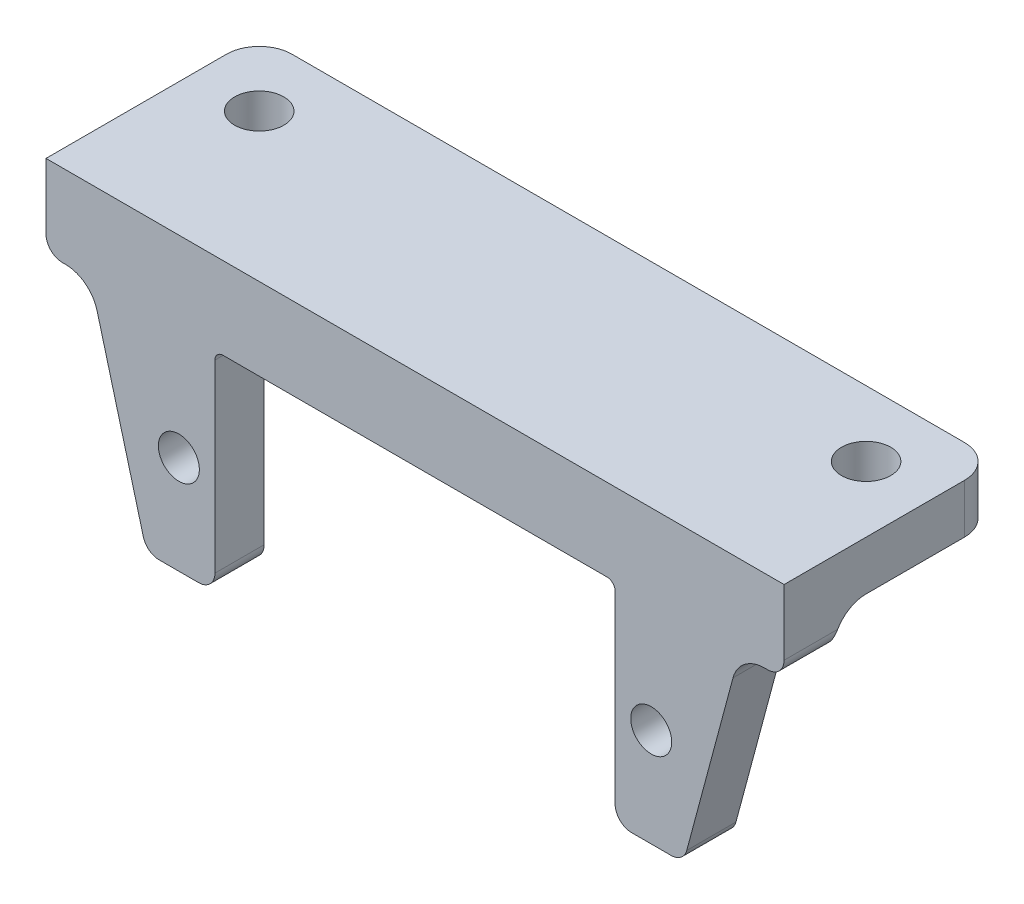
SolidWorks part; units mm, degrees
ref_plane "Front Plane" through (0, 0, 0) normal (0, 0, 1) x (1, 0, 0)
ref_plane "Top Plane" through (0, 0, 0) normal (0, 1, 0) x (1, 0, 0)
ref_plane "Right Plane" through (0, 0, 0) normal (1, 0, 0) x (0, 0, -1)
sketch "Sketch1" plane through (0, 0, 0) normal (0, 0, 1) x (1, 0, 0)
  line L1 (-15.9, -6.25) -> (15.9, -6.25)
  line L2 (-15.9, -6.25) -> (-15.9, 6.25)
  line L3 (-15.9, 6.25) -> (15.9, 6.25)
  line L4 (15.9, -6.25) -> (15.9, 6.25)
  line L5 (-15.9, -6.25) -> (15.9, 6.25) construction
  line L6 (-15.9, 6.25) -> (15.9, -6.25) construction
  line L7 (11.7, -6.25) -> (-11.7, -6.25)
  line L8 (11.7, -6.25) -> (11.7, 6.25)
  line L9 (11.7, 6.25) -> (-11.7, 6.25)
  line L10 (-11.7, -6.25) -> (-11.7, 6.25)
  line L11 (11.7, -6.25) -> (-11.7, 6.25) construction
  line L12 (11.7, 6.25) -> (-11.7, -6.25) construction
  circle A0 centre (-14.4, 0) radius 1
  circle A1 centre (-14.4, 3.5) radius 1
  circle A2 centre (-14.4, -3.5) radius 1
  circle A3 centre (14.4, 0) radius 1
  circle A4 centre (14.4, 3.5) radius 1
  circle A5 centre (14.4, -3.5) radius 1
  point P0 (0, 0)
  point P20 (0, 0)
  dimension "D3" = 2
  dimension "D1" = 31.8
  dimension "D2" = 12.5
  dimension "D4" = 1.5
  dimension "D5" = 3.5
  dimension "D6" = 3.5
  dimension "D7" = 1.5
  dimension "D8" = 23.4
sketch "Sketch3" plane through (0, 0, 0) normal (0, 0, 1) x (1, 0, 0)
  line L0 (-12.2, 6.25) -> (-12.2, -5)
  line L1 (-11.7, -6.25) -> (-11.7, 6.25) construction
  line L2 (-13.2, -6) -> (-15.6, -6)
  line L3 (-16.5659, -5.2588) -> (-19.3865, 5.2676)
  line L4 (12.2, 6.25) -> (12.2, -5)
  line L5 (11.7, -6.25) -> (11.7, 6.25) construction
  line L6 (13.2, -6) -> (15.6, -6)
  line L7 (16.5659, -5.2588) -> (19.3865, 5.2676)
  line L8 (-11.7, 6.75) -> (11.7, 6.75)
  line L9 (-15.9, 6.25) -> (15.9, 6.25) construction
  line L12 (-22.5, 11.75) -> (22.5, 11.75)
  line L14 (-21.3183, 6.75) -> (-21.5, 6.75)
  line L15 (-22.5, 7.75) -> (-22.5, 11.75)
  line L16 (21.3183, 6.75) -> (21.5, 6.75)
  line L17 (22.5, 7.75) -> (22.5, 11.75)
  circle A0 centre (-14.4, 0) radius 1.25
  circle A1 centre (14.4, 0) radius 1.25
  arc A2 (-12.2, -5) -> (-13.2, -6) centre (-13.2, -5) cw
  arc A3 (-15.6, -6) -> (-16.5659, -5.2588) centre (-15.6, -5) cw
  arc A4 (13.2, -6) -> (12.2, -5) centre (13.2, -5) cw
  arc A5 (16.5659, -5.2588) -> (15.6, -6) centre (15.6, -5) cw
  arc A6 (-11.7, 6.75) -> (-12.2, 6.25) centre (-11.7, 6.25) ccw
  arc A7 (12.2, 6.25) -> (11.7, 6.75) centre (11.7, 6.25) ccw
  arc A8 (-19.3865, 5.2676) -> (-21.3183, 6.75) centre (-21.3183, 4.75) ccw
  arc A9 (21.3183, 6.75) -> (19.3865, 5.2676) centre (21.3183, 4.75) ccw
  arc A10 (-21.5, 6.75) -> (-22.5, 7.75) centre (-21.5, 7.75) cw
  arc A11 (22.5, 7.75) -> (21.5, 6.75) centre (21.5, 7.75) cw
  point P16 (14.4, -6)
  point P22 (-12.2, -6)
  point P25 (-16.3673, -6)
  point P27 (-14.4, -6)
  point P30 (12.2, -6)
  point P46 (-19.7837, 6.75)
  point P49 (19.7837, 6.75)
  dimension "D1" = 2.5
  dimension "D9" = 1
  dimension "D10" = 1
  dimension "D11" = 1
  dimension "D6" = 1
  dimension "D12" = 0.5
  dimension "D13" = 0.5
  dimension "D14" = 2
  dimension "D15" = 2
  dimension "D16" = 1
  dimension "D17" = 1
  dimension "D2" = 0.5
  dimension "D3" = 75
  dimension "D4" = 0.5
  dimension "D8" = 0.5
  dimension "D5" = 6
  dimension "D7" = 75
  dimension "D19" = 5
  dimension "D18" = 45
extrude "Boss-Extrude1" add sketch "Sketch3" along normal blind 3
sketch "Sketch4" plane through (0, 0, 0) normal (0, 0, -1) x (-1, 0, 0)
  line L2 (22.5, 11.75) -> (22.5, 7.75) construction
  line L3 (-22.5, 11.75) -> (22.5, 11.75)
  line L4 (-22.5, 11.75) -> (-22.5, 8.75)
  line L5 (-22.5, 8.75) -> (22.5, 8.75)
  line L6 (22.5, 11.75) -> (22.5, 8.75)
  point P9 (-22.5, 8.75)
  point P12 (22.5, 8.75)
  dimension "D1" = 3
extrude "Boss-Extrude2" add sketch "Sketch4" along normal blind 10
fillet "Fillet1" radius 2 1 edges at (0, 8.75, 0)
fillet "Fillet2" radius 2 2 edges at (-22.5, 10.25, -10) (22.5, 10.25, -10)
sketch "Sketch5" plane through (0, 8.75, 0) normal (0, -1, 0) x (1, 0, 0)
  line L0 (-22.5, -8) -> (-22.5, -2) construction
  line L2 (20.5, -10) -> (-20.5, -10) construction
  circle A0 centre (-18.5, -6) radius 1.5
  dimension "D1" = 3
  dimension "D2" = 4
  dimension "D3" = 4
extrude "Cut-Extrude1" cut sketch "Sketch5" against normal through all
mirror "Mirror1" about plane through (0, 0, 0) normal (1, 0, 0) of "Cut-Extrude1"
equation "\"D6@Sketch1\"=\"D5@Sketch1\""
equation "\"D7@Sketch1\"=\"D4@Sketch1\""
equation "\"D4@Sketch3\"=\"D2@Sketch3\""
equation "\"D8@Sketch3\"=\"D2@Sketch3\""
